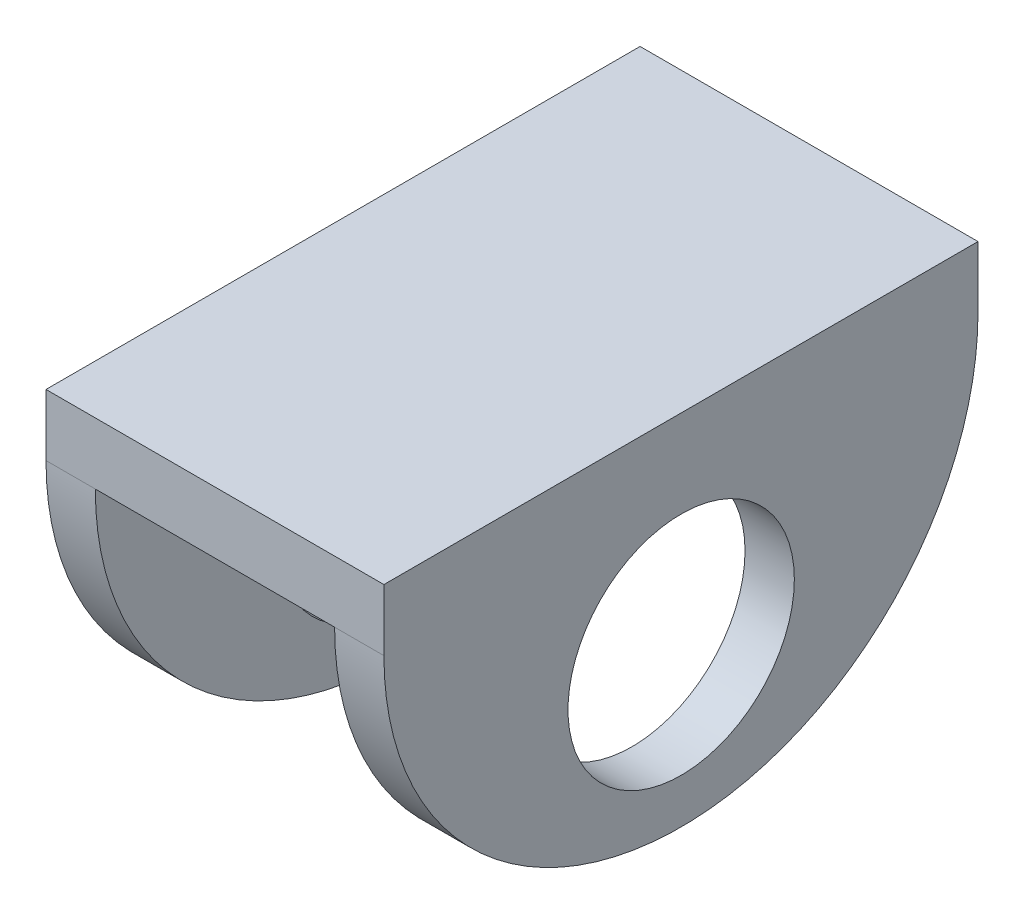
SolidWorks part; units mm, degrees
ref_plane "Front Plane" through (0, 0, 0) normal (0, 0, 1) x (1, 0, 0)
ref_plane "Top Plane" through (0, 0, 0) normal (0, 1, 0) x (1, 0, 0)
ref_plane "Right Plane" through (0, 0, 0) normal (1, 0, 0) x (0, 0, -1)
sketch "Sketch1" plane through (0, 0, 0) normal (1, 0, 0) x (0, 0, -1)
  line L0 (134.0536, 576.1345) -> (237.4936, 576.1345)
  line L1 (134.0536, 576.1345) -> (134.0536, 565.4124)
  line L2 (134.0536, 565.4124) -> (237.4936, 565.4124)
  line L3 (237.4936, 576.1345) -> (237.4936, 565.4124)
  point P2 (185.7736, 576.1345)
extrude "Boss-Extrude1" add sketch "Sketch1" along normal blind 20.8326 and the other way blind 20.8326
sketch "Sketch2" plane through (20.8326, 0, 0) normal (1, 0, 0) x (0, 0, -1)
  line L0 (134.0536, 565.4124) -> (134.0536, 576.1345)
  line L1 (134.0536, 576.1345) -> (237.4936, 576.1345)
  line L2 (237.4936, 576.1345) -> (237.4936, 565.4124)
  arc A0 (134.0536, 565.4124) -> (237.4936, 565.4124) centre (185.7736, 565.4124) ccw
  circle A1 centre (185.8117, 541.1889) radius 19.7049
  point P4 (185.7736, 513.4519)
  point P12 (166.1069, 541.1325)
extrude "Boss-Extrude2" add sketch "Sketch2" along normal blind 8.5862
mirror "Mirror1" about plane through (0, 0, 0) normal (1, 0, 0) of "Boss-Extrude2"
ref_axis "Axis1" through (0, 576.1345, -185.7736) along (0, 1, 0)
